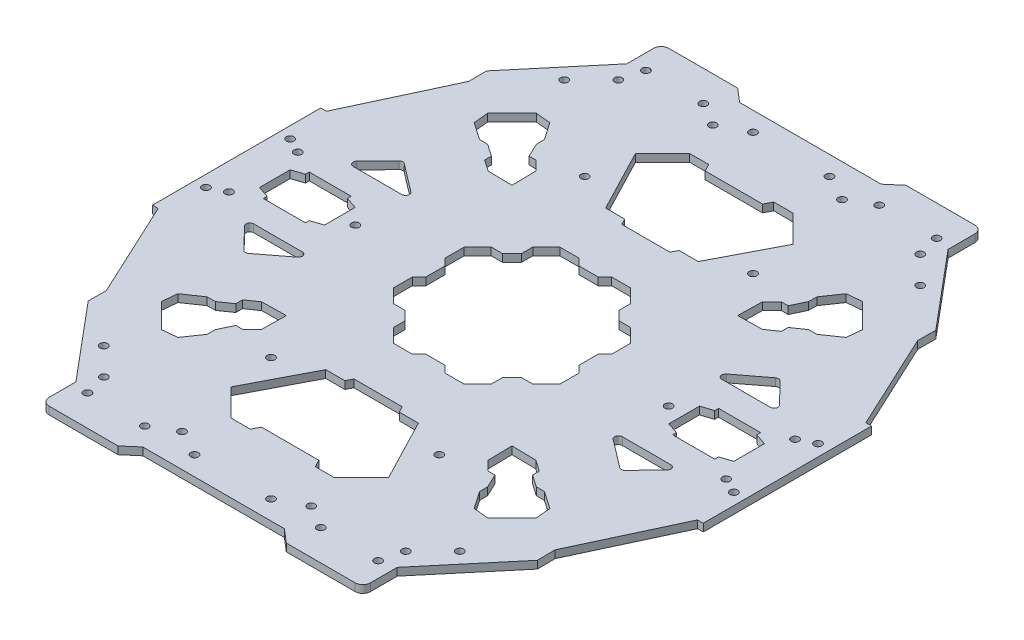
SolidWorks part; units mm, degrees
ref_plane "Front Plane" through (0, 0, 0) normal (0, 0, 1) x (1, 0, 0)
ref_plane "Top Plane" through (0, 0, 0) normal (0, 1, 0) x (1, 0, 0)
ref_plane "Right Plane" through (0, 0, 0) normal (1, 0, 0) x (0, 0, -1)
sketch "Sketch2" plane through (0, 0, 0) normal (0, 1, 0) x (1, 0, 0)
  line L0 (0, 78) -> (-18.5, 78)
  line L1 (-18.5, 78) -> (-22, 81)
  line L2 (-22, 81) -> (-40, 81)
  line L4 (-42, 72) -> (-58.7125, 52.0828)
  line L5 (-58.7125, 52.0828) -> (-58.6681, 47.3908)
  line L6 (-58.6681, 47.3908) -> (-70.5014, 22.0142)
  line L7 (-70.5014, 22.0142) -> (-72, 22)
  line L8 (-72, 22) -> (-72, 0)
  line L9 (-72, 0) -> (-62, 0) construction
  line L10 (0, 20) -> (0, 35) construction
  line L11 (0, 78) -> (0, 58)
  line L12 (-20, 0) -> (-45, 0)
  line L13 (-42, 79) -> (-42, 72)
  line L23 (-62, 0) -> (-62, 4)
  line L24 (-62, 4) -> (-59, 5)
  line L25 (-59, 5) -> (-59, 6)
  line L26 (-59, 6) -> (-48, 6)
  line L27 (-48, 6) -> (-48, 5)
  line L28 (-48, 5) -> (-45, 4)
  line L29 (-45, 4) -> (-45, 0)
  line L30 (-59, 5) -> (-48, 5) construction
  line L31 (-62, 4) -> (-45, 4) construction
  line L32 (-62, 0) -> (-72, 0)
  line L33 (-45, 0) -> (-20, 0) construction
  line L34 (-20, 0) -> (-20, 2.5)
  line L35 (-20, 2.5) -> (-21.7678, 4.2678)
  line L36 (-21.7678, 4.2678) -> (-21.7678, 9.2678)
  line L37 (-21.7678, 9.2678) -> (-18.2322, 12.8033)
  line L38 (-18.2322, 12.8033) -> (-15.2322, 12.8033)
  line L39 (-15.2322, 12.8033) -> (-12.8033, 15.2322)
  line L40 (-12.8033, 15.2322) -> (-12.8033, 18.2322)
  line L41 (-12.8033, 18.2322) -> (-9.2678, 21.7678)
  line L42 (-9.2678, 21.7678) -> (-4.2678, 21.7678)
  line L43 (-4.2678, 21.7678) -> (-2.5, 20)
  line L44 (-2.5, 20) -> (0, 20)
  line L45 (0, 58) -> (-7.5, 58)
  line L46 (-7.5, 58) -> (-8.5, 59.9227)
  line L47 (-8.5, 59.9227) -> (-13.5, 59.9227)
  line L48 (-13.5, 59.9227) -> (-20.5711, 52.8516)
  line L49 (-20.5711, 52.8516) -> (-12.1097, 36.5829)
  line L50 (-12.1097, 36.5829) -> (-7.1097, 36.5829)
  line L51 (-7.1097, 36.5829) -> (-6.2864, 35)
  line L52 (-6.2864, 35) -> (0, 35)
  line L53 (0, 58) -> (0, 78) construction
  line L54 (0, 35) -> (0, 20)
  line L55 (0, 20) -> (0, 0) construction
  line L56 (0, 0) -> (-20, 0) construction
  line L57 (-38, 73) -> (-23, 73) construction
  line L58 (-23, 73) -> (-10, 73) construction
  line L59 (-10, 73) -> (0, 73) construction
  line L60 (-39.4554, 67.254) -> (-46.5264, 60.1829) construction
  line L61 (-39.4554, 67.254) -> (-43.2856, 70.4679) construction
  line L62 (-54.5154, 13) -> (-41.8398, 13)
  line L63 (-41.2331, 14.7949) -> (-48.5098, 20.3496)
  line L64 (-49.8336, 20.2517) -> (-55.2325, 14.697)
  line L65 (0, 0) -> (-100.3745, 100.3745) construction
  line L66 (-49.0044, 42.6404) -> (-42.6404, 49.0044)
  line L67 (-42.6404, 49.0044) -> (-38.7306, 48.6301)
  line L68 (-38.7306, 48.6301) -> (-35.6207, 44.106)
  line L69 (-35.6207, 44.106) -> (-35.5818, 41.9458)
  line L70 (-35.5818, 41.9458) -> (-33.8755, 38.328)
  line L71 (-33.8755, 38.328) -> (-32.1077, 38.328)
  line L72 (-32.1077, 38.328) -> (-29.6107, 35.831)
  line L73 (-29.6107, 35.831) -> (-29.4969, 29.4969)
  line L74 (-29.4969, 29.4969) -> (-35.831, 29.6107)
  line L75 (-35.831, 29.6107) -> (-38.7906, 31.6451)
  line L76 (-38.7906, 31.6451) -> (-38.7906, 33.4129)
  line L77 (-38.7906, 33.4129) -> (-41.9458, 35.5818)
  line L78 (-41.9458, 35.5818) -> (-44.106, 35.6207)
  line L79 (-44.106, 35.6207) -> (-48.6301, 38.7306)
  line L80 (-48.6301, 38.7306) -> (-49.0044, 42.6404)
  line L81 (-38.7306, 48.6301) -> (-48.6301, 38.7306) construction
  line L82 (-44.106, 35.6207) -> (-35.6207, 44.106) construction
  line L83 (-35.5818, 41.9458) -> (-41.9458, 35.5818) construction
  line L84 (-38.7906, 33.4129) -> (-33.8755, 38.328) construction
  line L85 (-32.1077, 38.328) -> (-38.7906, 31.6451) construction
  line L86 (-35.831, 29.6107) -> (-29.6107, 35.831) construction
  arc A0 (-40, 81) -> (-42, 79) centre (-40, 79) ccw
  circle A1 centre (-38, 73) radius 1
  circle A2 centre (-23, 73) radius 1
  circle A3 centre (-10, 73) radius 1
  circle A4 centre (-16.8822, 69.3859) radius 1
  circle A5 centre (-46.5264, 60.1829) radius 1
  circle A6 centre (-40.9575, 0) radius 1
  circle A7 centre (-39.4554, 67.254) radius 1
  arc A8 (-41.8398, 13) -> (-41.2331, 14.7949) centre (-41.8398, 14) ccw
  arc A9 (-48.5098, 20.3496) -> (-49.8336, 20.2517) centre (-49.1165, 19.5548) ccw
  arc A10 (-54.5154, 13) -> (-55.2325, 14.697) centre (-54.5154, 14) cw
  circle A11 centre (-69, 11) radius 1
  circle A12 centre (-65, 9) radius 1
  circle A13 centre (-22, 41) radius 1
  point P25 (-42, 81)
  point P63 (-38.8818, 13)
  point P68 (-49.2151, 20.8881)
  point P71 (-56.8818, 13)
  point P93 (-43.6804, 43.6804)
  point P94 (-39.8633, 39.8633)
  point P95 (-45.8224, 45.8224)
  point P96 (-38.7638, 38.7638)
  point P98 (-13.3946, 32.5368)
  point P99 (-32.7209, 32.7209)
  dimension "D13" = 2
  dimension "D41" = 15
  dimension "D52" = 1
  dimension "D63" = 41
  dimension "D1" = 81
  dimension "D2" = 72
  dimension "D3" = 18.5
  dimension "D4" = 20
  dimension "D5" = 9
  dimension "D6" = 22
  dimension "D7" = 26
  dimension "D8" = 28
  dimension "D9" = 50
  dimension "D10" = 25
  dimension "D11" = 42
  dimension "D12" = 3
  dimension "D14" = 2.5
  dimension "D15" = 20
  dimension "D16" = 2.5
  dimension "D17" = 45
  dimension "D18" = 5
  dimension "D19" = 2.5
  dimension "D20" = 5
  dimension "D21" = 20
  dimension "D22" = 17
  dimension "D23" = 6
  dimension "D24" = 3
  dimension "D25" = 3
  dimension "D26" = 4
  dimension "D27" = 1
  dimension "D28" = 10
  dimension "D29" = 5
  dimension "D30" = 2.5
  dimension "D31" = 3
  dimension "D32" = 5
  dimension "D33" = 20
  dimension "D34" = 23
  dimension "D35" = 5
  dimension "D36" = 7.5
  dimension "D37" = 1
  dimension "D38" = 10
  dimension "D39" = 45
  dimension "D40" = 5
  dimension "D42" = 13
  dimension "D43" = 10
  dimension "D44" = 5
  dimension "D45" = 5
  dimension "D46" = 10
  dimension "D47" = 2
  dimension "D48" = 18
  dimension "D49" = 13
  dimension "D50" = 11
  dimension "D51" = 7
  dimension "D53" = 11
  dimension "D54" = 9
  dimension "D55" = 3
  dimension "D56" = 4
  dimension "D57" = 45
  dimension "D58" = 14
  dimension "D59" = 9
  dimension "D60" = 9
  dimension "D61" = 12
  dimension "D62" = 45
  dimension "D64" = 22
extrude "Boss-Extrude1" add sketch "Sketch2" along normal blind 2 contours A6 L12 L34 L35 L36 L37 L38 L39 L40 L41 L42 L43 L44 L54 L52 L51 L50 L49 L48 L47 L46 L45 L11 L0 L1 L2 A0 L13 L4 L5 L6 L7 L8 L32 L23 L24 L25 L26 L27 L28 L29 A7 A5 A4 A3 region at (-1.0837, 0, -68)
mirror "Mirror2" about plane through (0, 0, 0) normal (1, 0, 0) of "Boss-Extrude1" second plane through (0, 0, 0) second plane normal (0, 0, 1)
